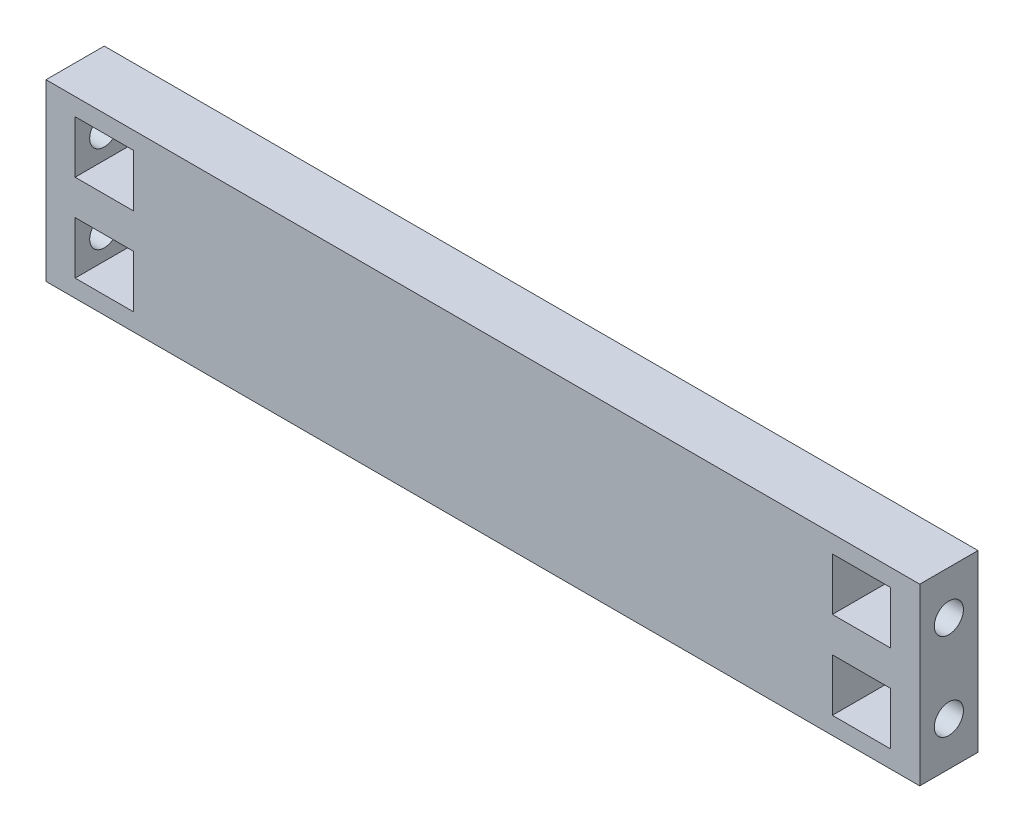
SolidWorks part; units mm, degrees
material "6061-T6 (SS)"
ref_plane "Front Plane" through (0, 0, 0) normal (0, 0, 1) x (1, 0, 0)
ref_plane "Top Plane" through (0, 0, 0) normal (0, 1, 0) x (1, 0, 0)
ref_plane "Right Plane" through (0, 0, 0) normal (1, 0, 0) x (0, 0, -1)
sketch "Sketch1" plane through (0, 0, 0) normal (0, 0, 1) x (1, 0, 0)
  line L1 (-95.25, -19.05) -> (95.25, -19.05)
  line L2 (-95.25, -19.05) -> (-95.25, 19.05)
  line L3 (-95.25, 19.05) -> (95.25, 19.05)
  line L4 (95.25, -19.05) -> (95.25, 19.05)
  line L5 (-95.25, -19.05) -> (95.25, 19.05) construction
  line L6 (-95.25, 19.05) -> (95.25, -19.05) construction
  point P0 (0, 0)
  dimension "D1" = 38.1
  dimension "D2" = 190.5
extrude "Boss-Extrude1" add sketch "Sketch1" along normal blind 12.7 contours L4 L3 L2 L1 region at (0, 0, 0)
sketch "Sketch2" plane through (0, 0, 12.7) normal (0, 0, 1) x (1, 0, 0)
  line L0 (-95.25, 19.05) -> (95.25, 19.05) construction
  line L1 (-88.9, 15.24) -> (-76.2, 15.24)
  line L2 (-88.9, 15.24) -> (-88.9, 3.81)
  line L3 (-88.9, 3.81) -> (-76.2, 3.81)
  line L4 (-76.2, 15.24) -> (-76.2, 3.81)
  line L5 (-88.9, -3.81) -> (-76.2, -3.81)
  line L6 (-88.9, -3.81) -> (-88.9, -15.24)
  line L7 (-88.9, -15.24) -> (-76.2, -15.24)
  line L8 (-76.2, -3.81) -> (-76.2, -15.24)
  line L9 (88.9, 3.81) -> (76.2, 3.81)
  line L10 (88.9, 3.81) -> (88.9, 15.24)
  line L11 (88.9, 15.24) -> (76.2, 15.24)
  line L12 (76.2, 3.81) -> (76.2, 15.24)
  line L13 (76.2, -3.81) -> (88.9, -3.81)
  line L14 (76.2, -3.81) -> (76.2, -15.24)
  line L15 (76.2, -15.24) -> (88.9, -15.24)
  line L16 (88.9, -3.81) -> (88.9, -15.24)
  line L17 (-95.25, -19.05) -> (95.25, -19.05) construction
  line L18 (-95.25, -19.05) -> (-95.25, 19.05) construction
  line L19 (95.25, -19.05) -> (95.25, 19.05) construction
  point P16 (-88.9, 9.525)
  point P17 (-88.9, -9.525)
  point P26 (88.9, 9.525)
  point P27 (88.9, -9.525)
  dimension "D1" = 11.43
  dimension "D2" = 9.525
  dimension "D3" = 9.525
  dimension "D4" = 6.35
  dimension "D5" = 6.35
  dimension "D6" = 6.35
  dimension "D7" = 6.35
  dimension "D8" = 9.525
  dimension "D9" = 9.525
  dimension "D10" = 12.7
extrude "Cut-Extrude1" cut sketch "Sketch2" against normal through all
sketch "Sketch3" plane through (-95.25, 0, 0) normal (-1, 0, 0) x (0, 0, 1)
  line L0 (12.7, 19.05) -> (0, 19.05) construction
  line L1 (12.7, -19.05) -> (12.7, 19.05) construction
  line L2 (12.7, -19.05) -> (0, -19.05) construction
  circle A0 centre (6.35, 9.525) radius 3.175
  circle A1 centre (6.35, -9.525) radius 3.175
  dimension "D1" = 6.35
  dimension "D4" = 6.35
  dimension "D2" = 9.525
  dimension "D3" = 6.35
  dimension "D5" = 6.35
  dimension "D6" = 9.525
extrude "Cut-Extrude2" cut sketch "Sketch3" against normal up to surface (6.35 mm away) up to face at (-88.9, 9.525, 6.35)
sketch "Sketch4" plane through (95.25, 0, 0) normal (1, 0, 0) x (0, 0, -1)
  circle A0 centre (-6.35, -9.525) radius 3.175 construction
  circle A1 centre (-6.35, 9.525) radius 3.175 construction
  circle A2 centre (-6.35, -9.525) radius 3.175
  circle A3 centre (-6.35, 9.525) radius 3.175
extrude "Cut-Extrude3" cut sketch "Sketch4" against normal up to surface (6.35 mm away) up to face at (88.9, 9.525, 6.35)
